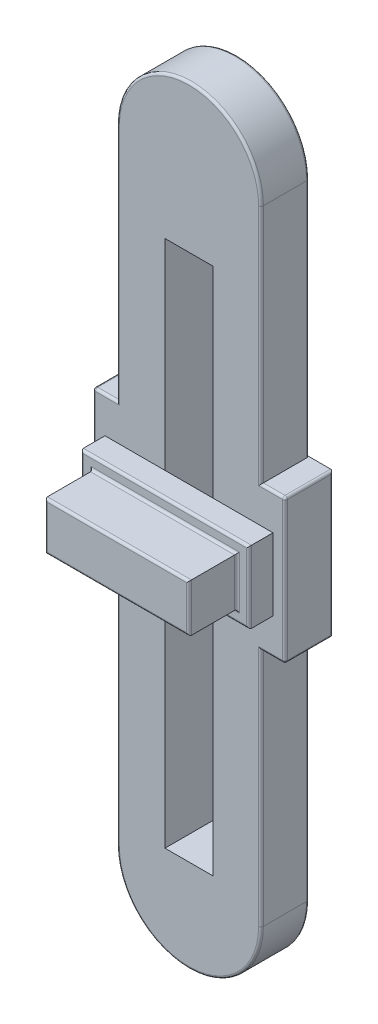
SolidWorks part; units mm, degrees
ref_plane "Front Plane" through (0, 0, 0) normal (0, 0, 1) x (1, 0, 0)
ref_plane "Top Plane" through (0, 0, 0) normal (0, 1, 0) x (1, 0, 0)
ref_plane "Right Plane" through (0, 0, 0) normal (1, 0, 0) x (0, 0, -1)
sketch "Sketch1" plane through (0, 0, 0) normal (0, 0, 1) x (1, 0, 0)
  line L0 (0, 0) -> (0, -6604) construction
  line L1 (762, 0) -> (762, -2540)
  line L2 (-762, 0) -> (-762, -2540)
  line L3 (0, -795.1535) -> (-254, -795.1535)
  line L8 (-254, -795.1535) -> (-254, -6383.1535)
  line L9 (-254, -6383.1535) -> (0, -6383.1535)
  line L10 (0, -6383.1535) -> (254, -6383.1535)
  line L11 (254, -6383.1535) -> (254, -795.1535)
  line L12 (254, -795.1535) -> (0, -795.1535)
  line L13 (-762, -3302) -> (762, -3302) construction
  line L14 (-762, -4064) -> (-762, -6604)
  line L15 (-762, -2540) -> (-1016, -2540)
  line L17 (-762, -4064) -> (-1016, -4064)
  line L18 (-1016, -2540) -> (-1016, -4064)
  line L19 (762, -2540) -> (1016, -2540)
  line L21 (762, -4064) -> (1016, -4064)
  line L22 (1016, -2540) -> (1016, -4064)
  line L23 (762, -4064) -> (762, -6604)
  arc A0 (762, 0) -> (-762, 0) centre (0, 0) ccw
  arc A1 (-762, -6604) -> (762, -6604) centre (0, -6604) ccw
  point P3 (0, -3302)
  dimension "D2" = 762
  dimension "D1" = 6604
  dimension "D3" = 254
  dimension "D4" = 254
  dimension "D5" = 5588
  dimension "D6" = 254
  dimension "D7" = 1524
  dimension "D8" = 508
extrude "Boss-Extrude1" add sketch "Sketch1" along normal blind 508
sketch "Sketch2" plane through (0, 0, 508) normal (0, 0, 1) x (1, 0, 0)
  line L0 (-1016, -3302) -> (1016, -3302) construction
  line L1 (-1016, -2540) -> (-1016, -4064) construction
  line L2 (1016, -4064) -> (1016, -2540) construction
  line L4 (-762, -3048) -> (762, -3048)
  line L5 (-762, -3048) -> (-762, -3556)
  line L6 (-762, -3556) -> (762, -3556)
  line L7 (762, -3048) -> (762, -3556)
  line L8 (-762, -3048) -> (762, -3556) construction
  line L9 (-762, -3556) -> (762, -3048) construction
  point P6 (0, -3302)
  dimension "D1" = 1524
  dimension "D2" = 508
extrude "Boss-Extrude3" add sketch "Sketch2" along normal blind 762
sketch "Sketch3" plane through (0, 0, 508) normal (0, 0, 1) x (1, 0, 0)
  line L4 (762, -3556) -> (762, -3048)
  line L5 (762, -3048) -> (-762, -3048)
  line L6 (-762, -3048) -> (-762, -3556)
  line L7 (-762, -3556) -> (762, -3556)
  line L8 (762, -3556) -> (762, -3048)
  line L9 (762, -3048) -> (-762, -3048)
  line L10 (-762, -3048) -> (-762, -3556)
  line L11 (-762, -3556) -> (762, -3556)
  line L20 (889, -3683) -> (889, -2921)
  line L21 (889, -2921) -> (-889, -2921)
  line L22 (-889, -2921) -> (-889, -3683)
  line L23 (-889, -3683) -> (889, -3683)
  line L24 (889, -3683) -> (889, -2921)
  line L25 (889, -2921) -> (-889, -2921)
  line L26 (-889, -2921) -> (-889, -3683)
  line L27 (-889, -3683) -> (889, -3683)
  dimension "D1" = 0
  dimension "D2" = 127
extrude "Boss-Extrude4" add sketch "Sketch3" along normal blind 254
fillet "Fillet1" radius 25.4 12 edges at (0, -3048, 762) (-762, -3302, 762) (0, -3556, 762) (762, -3302, 762) (-889, -3302, 762) (0, -2921, 762) (889, -3302, 762) (0, -3683, 762) (0, -3556, 1270) (-762, -3302, 1270) (0, -3048, 1270) (762, -3302, 1270)
fillet "Fillet2" radius 25.4 24 edges at (1016, -4064, 254) (-889, -2540, 0) (-889, -2540, 508) (0, -7366, 508) (0, -7366, 0) (-762, -1270, 508) (-762, -1270, 0) (0, 762, 508) (0, 762, 0) (762, -1270, 0) (-889, -4064, 0) (-889, -4064, 508) (-1016, -3302, 508) (-1016, -3302, 0) (-762, -5334, 0) (-762, -5334, 508) (762, -5334, 0) (1016, -3302, 0) (1016, -2540, 254) (762, -1270, 508) (889, -2540, 508) (889, -4064, 508) (762, -5334, 508) (1016, -3302, 508)
fillet "Fillet3" radius 25.4 6 edges at (-1008.5605, -4056.5605, 500.5605) (-1008.5605, -4056.5605, 7.4395) (-1008.5605, -2547.4395, 500.5605) (-1008.5605, -2547.4395, 7.4395) (-1016, -4064, 254) (-1016, -2540, 254)
